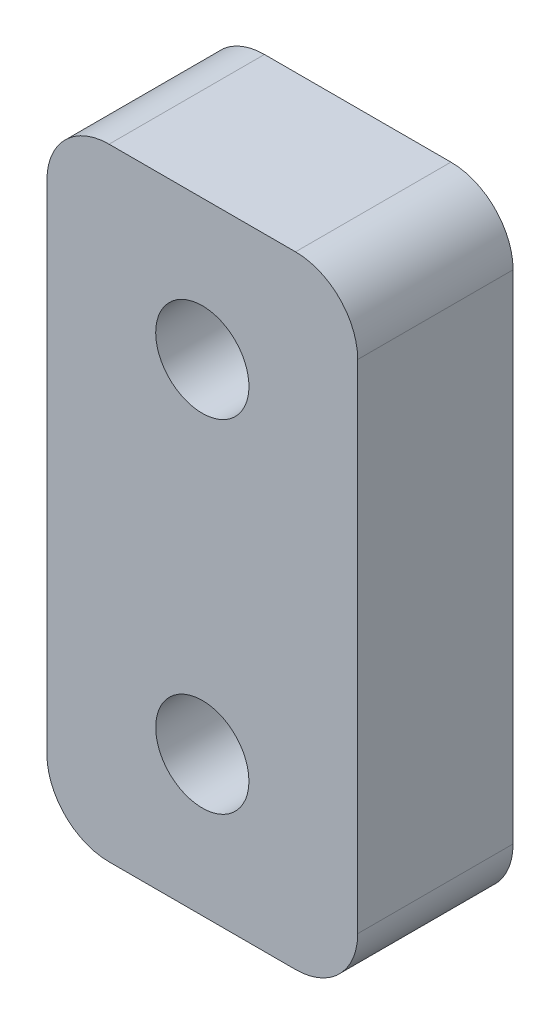
SolidWorks part; units mm, degrees
ref_plane "前视基准面" through (0, 0, 0) normal (0, 0, 1) x (1, 0, 0)
ref_plane "上视基准面" through (0, 0, 0) normal (0, 1, 0) x (1, 0, 0)
ref_plane "右视基准面" through (0, 0, 0) normal (1, 0, 0) x (0, 0, -1)
sketch "草图2" plane through (0, 0, 0) normal (0, 0, 1) x (1, 0, 0)
  line L1 (5, -10) -> (-5, -10)
  line L2 (5, -10) -> (5, 10)
  line L3 (5, 10) -> (-5, 10)
  line L4 (-5, -10) -> (-5, 10)
  line L5 (5, -10) -> (-5, 10) construction
  line L6 (5, 10) -> (-5, -10) construction
  point P0 (0, 0)
  dimension "D1" = 10
  dimension "D2" = 20
extrude "凸台-拉伸1" add sketch "草图2" along normal blind 5
sketch "草图3" plane through (0, 0, 5) normal (0, 0, 1) x (1, 0, 0)
  line L0 (0, -10) -> (0, -5.5) construction
  line L1 (-5, -10) -> (5, -10) construction
  line L2 (0, 0) -> (5, 0) construction
  line L3 (5, -10) -> (5, 10) construction
  line L4 (0, 10) -> (0, 5.5) construction
  circle A0 centre (0, -5.5) radius 1.5
  circle A1 centre (0, 5.5) radius 1.5
  dimension "D1" = 3
  dimension "D2" = 4.5
extrude "切除-拉伸1" cut sketch "草图3" against normal through all
fillet "圆角1" radius 2 4 edges at (5, -10, 2.5) (-5, -10, 2.5) (5, 10, 2.5) (-5, 10, 2.5)
